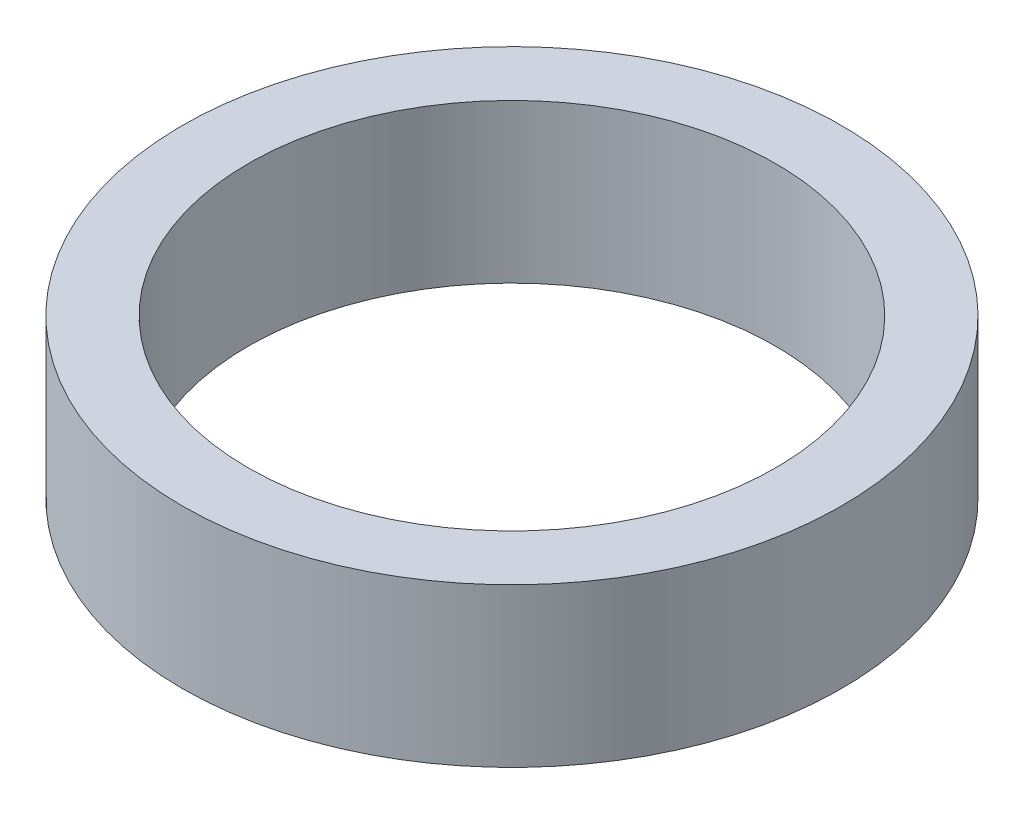
SolidWorks part; units mm, degrees
ref_plane "Front Plane" through (0, 0, 0) normal (0, 0, 1) x (1, 0, 0)
ref_plane "Top Plane" through (0, 0, 0) normal (0, 1, 0) x (1, 0, 0)
ref_plane "Right Plane" through (0, 0, 0) normal (1, 0, 0) x (0, 0, -1)
sketch "Sketch1" plane through (0, 0, 0) normal (0, 1, 0) x (1, 0, 0)
  circle A0 centre (0, 0) radius 62.5
  dimension "FLANGE_OD" = 125
extrude "Boss-Extrude1" add sketch "Sketch1" along normal blind 30
sketch "Sketch2" plane through (0, 0, 0) normal (0, 1, 0) x (1, 0, 0)
  circle A0 centre (0, 0) radius 50
  dimension "BORE_D" = 100
extrude "Cut-Extrude1" cut sketch "Sketch2" along normal through all
sketch "Sketch3" plane through (0, 30, 0) normal (0, 1, 0) x (1, 0, 0)
  circle A0 centre (0, 0) radius 28.316 construction
  circle A1 centre (-28.316, 0) radius 1.9523
  dimension "BOLT_D" = 3.9045
  dimension "BOLT_PCD" = 56.6319
extrude "Cut-Extrude2" cut sketch "Sketch3" against normal blind 18.5208 rebuild error yes
pattern_circular "CirPattern1" count 4 over 360 rebuild error yes
